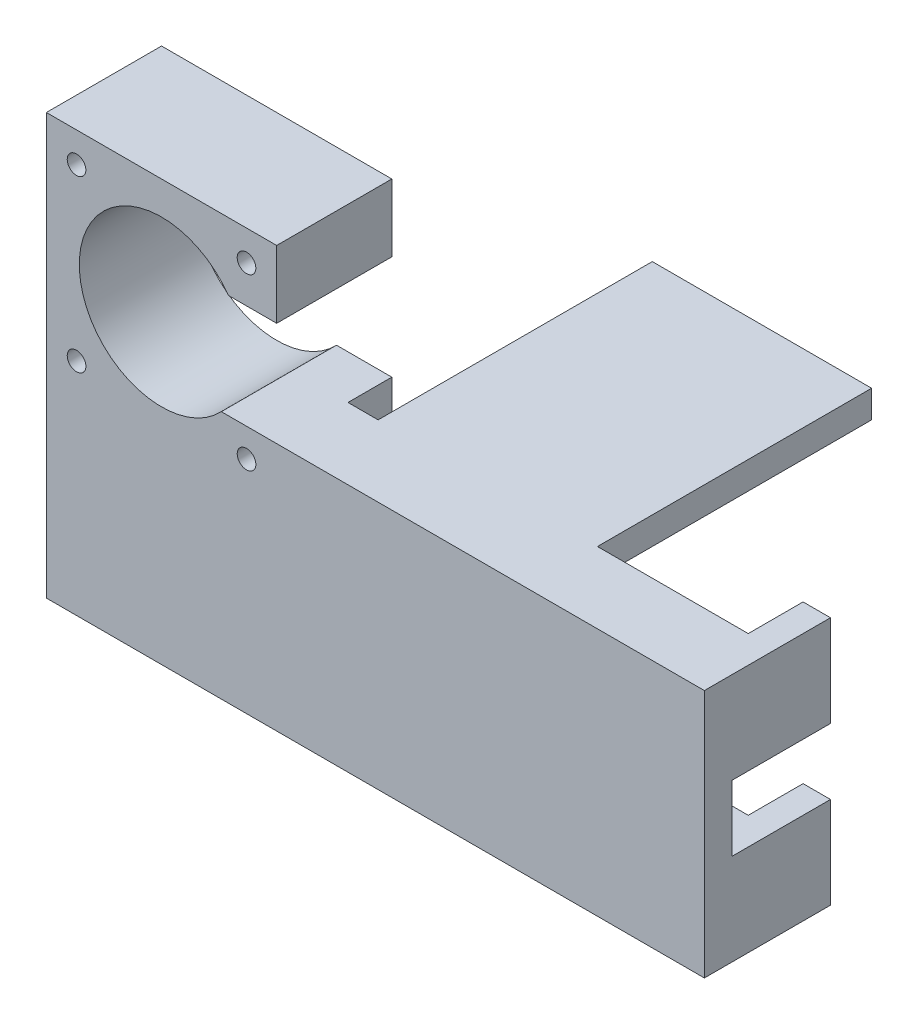
SolidWorks part; units mm, degrees
ref_plane "Front Plane" through (0, 0, 0) normal (0, 0, 1) x (1, 0, 0)
ref_plane "Top Plane" through (0, 0, 0) normal (0, 1, 0) x (1, 0, 0)
ref_plane "Right Plane" through (0, 0, 0) normal (1, 0, 0) x (0, 0, -1)
sketch "Sketch1" plane through (0, 0, 0) normal (0, 0, 1) x (1, 0, 0)
  line L1 (0, 0) -> (120, 0)
  line L2 (0, 0) -> (0, 45.4)
  line L3 (0, 45.4) -> (120, 45.4)
  line L4 (120, 0) -> (120, 45.4)
  dimension "D1" = 120
  dimension "D2" = 45.4
extrude "Boss-Extrude1" add sketch "Sketch1" along normal blind 13 contours L2 L3 L4 L1
sketch "Sketch2" plane through (0, 0, 0) normal (0, 0, -1) x (-1, 0, 0)
  line L0 (0, 0) -> (-120, 0) construction
  line L1 (-120, 45.4) -> (-115, 45.4)
  line L2 (-120, 45.4) -> (-120, 0)
  line L3 (-120, 0) -> (-115, 0)
  line L4 (-115, 45.4) -> (-115, 0)
  dimension "D1" = 5
extrude "Boss-Extrude2" add sketch "Sketch2" along normal blind 10
sketch "Sketch3" plane through (0, 0, 0) normal (0, 0, 1) x (1, 0, 0)
  line L0 (0, 0) -> (0, 45.4) construction
  line L1 (0, 28.7) -> (120, 28.7)
  line L2 (0, 28.7) -> (0, 16.7)
  line L3 (0, 16.7) -> (120, 16.7)
  line L4 (120, 28.7) -> (120, 16.7)
  line L5 (120, 45.4) -> (120, 0) construction
  line L7 (0, 0) -> (115, 0) construction
  dimension "D1" = 12
  dimension "D2" = 16.7
extrude "Cut-Extrude1" cut sketch "Sketch3" against normal through all and the other way blind 8
sketch "Sketch4" plane through (0, 0, 0) normal (0, 0, -1) x (-1, 0, 0)
  line L1 (0, 28.7) -> (-42, 28.7)
  line L2 (0, 28.7) -> (0, 76.7)
  line L3 (0, 76.7) -> (-42, 76.7)
  line L4 (-42, 28.7) -> (-42, 76.7)
  dimension "D1" = 42
  dimension "D2" = 48
extrude "Boss-Extrude3" add sketch "Sketch4" along normal blind 8 and the other way up to surface (13 mm away) other way up to face at (60, 22.7, 13)
sketch "Sketch5" plane through (0, 0, -8) normal (0, 0, -1) x (-1, 0, 0)
  line L0 (0, 55.7) -> (-42, 55.7) construction
  line L3 (-21, 76.7) -> (-21, 28.7) construction
  line L4 (0, 76.7) -> (-42, 76.7) construction
  line L5 (-42, 28.7) -> (0, 28.7) construction
  line L7 (-36.5, 40.2) -> (-5.5, 40.2) construction
  line L8 (-36.5, 40.2) -> (-36.5, 71.2) construction
  line L9 (-36.5, 71.2) -> (-5.5, 71.2) construction
  line L10 (-5.5, 40.2) -> (-5.5, 71.2) construction
  line L11 (-36.5, 40.2) -> (-5.5, 71.2) construction
  line L12 (-36.5, 71.2) -> (-5.5, 40.2) construction
  circle A0 centre (-21, 55.7) radius 15
  circle A1 centre (-36.5, 71.2) radius 1.7
  circle A2 centre (-5.5, 71.2) radius 1.7
  circle A3 centre (-5.5, 40.2) radius 1.7
  circle A4 centre (-36.5, 40.2) radius 1.7
  point P2 (0, 0)
  dimension "D1" = 30
  dimension "D4" = 3.4
  dimension "D2" = 31
  dimension "D3" = 31
  dimension "D5" = 21
extrude "Cut-Extrude2" cut sketch "Sketch5" against normal through all
sketch "Sketch6" plane through (0, 0, 13) normal (0, 0, 1) x (1, 0, 0)
  line L7 (42, 45.4) -> (120, 45.4) construction
  line L8 (42, 45.4) -> (20, 45.4)
  line L9 (42, 45.4) -> (42, 64.4)
  line L10 (42, 64.4) -> (20, 64.4)
  line L11 (20, 45.4) -> (20, 64.4)
  line L12 (42, 76.7) -> (42, 45.4) construction
  line L13 (0, 0) -> (0, 76.7) construction
  dimension "D1" = 19
  dimension "D2" = 20
extrude "Cut-Extrude3" cut sketch "Sketch6" against normal through all
sketch "Sketch7" plane through (0, 0, 0) normal (0, 0, -1) x (-1, 0, 0)
  line L0 (-42, 45.4) -> (-42, 28.7) construction
  line L1 (-47.5, 45.4) -> (-87.5, 45.4)
  line L2 (-47.5, 45.4) -> (-47.5, 40.4)
  line L3 (-47.5, 40.4) -> (-87.5, 40.4)
  line L4 (-87.5, 45.4) -> (-87.5, 40.4)
  line L5 (-42, 45.4) -> (-115, 45.4) construction
  dimension "D1" = 5
  dimension "D2" = 40
  dimension "D3" = 5.5
extrude "Boss-Extrude4" add sketch "Sketch7" along normal blind 50
